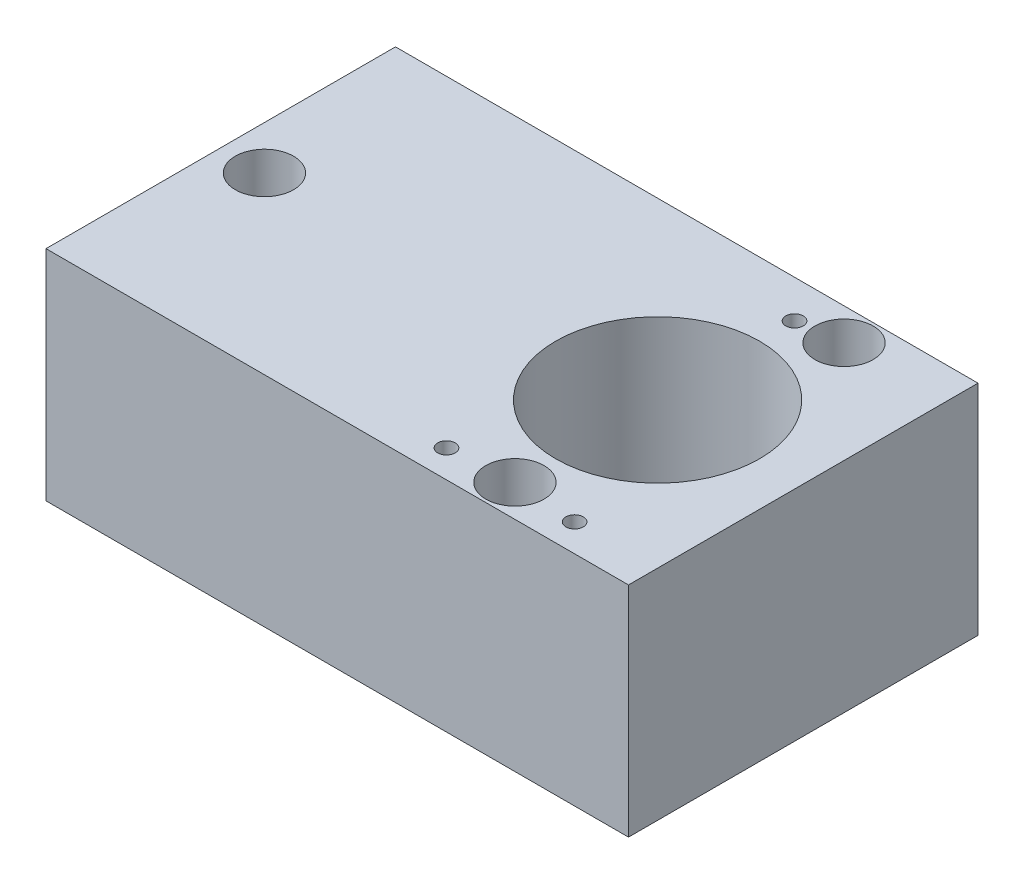
SolidWorks part; units mm, degrees
ref_plane "前视基准面" through (0, 0, 0) normal (0, 0, 1) x (1, 0, 0)
ref_plane "上视基准面" through (0, 0, 0) normal (0, 1, 0) x (1, 0, 0)
ref_plane "右视基准面" through (0, 0, 0) normal (1, 0, 0) x (0, 0, -1)
other "Configuration Table"
sketch "草图1" plane through (0, 0, 0) normal (0, 1, 0) x (1, 0, 0)
  line L0 (7.8359, -6) -> (30.681, -6) construction
  line L1 (0, 0) -> (20, 0)
  line L2 (0, 0) -> (0, -12)
  line L3 (0, -12) -> (20, -12)
  line L4 (20, 0) -> (20, -12)
  circle A7 centre (5, -6) radius 1
  circle A8 centre (8.3407, -8.2) radius 0.55
  circle A9 centre (10.7299, -3.8078) radius 0.55
  circle A10 centre (15, -6) radius 2.55
  circle A11 centre (15, -6) radius 3.5
  point P5 (5, -6)
  point P16 (0, 0)
  point P17 (0, 0)
  point P19 (0, 0)
  point P20 (0, 0)
  dimension "D4" = 1.1
  dimension "D6" = 7
  dimension "D8" = 2
  dimension "D3" = 1.1
  dimension "D5" = 5.1
  dimension "D2" = 5
  dimension "D7" = 20
  dimension "D10" = 5
  dimension "D12" = 12
extrude "凸台-拉伸1" add sketch "草图1" along normal blind 2.5 contours L4 L3 L2 L1
extrude "切除-拉伸3" cut sketch "草图1<9>" along normal blind 2.5 contours A9 | A10 | A8
sketch "草图1<9>" plane through (0, 0, 0) normal (0, 1, 0) x (1, 0, 0) same geometry as "草图1"
extrude "凸台-拉伸2" add sketch "草图1<10>" along normal blind 5 from surface contours L1 L4 L3 L2 | A11 starting at face at (8.3407, 2.5, 8.75)
sketch "草图1<10>" plane through (0, 0, 0) normal (0, 1, 0) x (1, 0, 0) same geometry as "草图1"
sketch "草图2" plane through (0, 0, 0) normal (0, -1, 0) x (1, 0, 0)
  circle A0 centre (15, 10.9) radius 0.7
  circle A1 centre (1.5, 6) radius 0.7
  circle A2 centre (16.5, 1.1) radius 0.7
  circle A3 centre (16.5, 1.1) radius 1
  circle A4 centre (15, 10.9) radius 1
  circle A5 centre (1.5, 6) radius 1
  circle A9 centre (12.8, 11.05) radius 0.3
  circle A16 centre (17.2, 11.05) radius 0.3
  circle A17 centre (15, 1.3) radius 0.3
  circle A18 centre (1.5, 6) radius 0.3
  dimension "D1" = 1.4
  dimension "D2" = 2
  dimension "D3" = 0.6
extrude "切除-拉伸4" cut sketch "草图2" against normal through all contours A0 | A2 | A1
extrude "切除-拉伸5" cut sketch "草图2<3>" along normal offset from surface (5.5 mm away) 2 from surface contours A4 | A5 | A3 up to face at (15, 0, 10.2) starting at face at (15, 7.5, 10.2)
sketch "草图2<3>" plane through (0, 0, 0) normal (0, -1, 0) x (1, 0, 0) same geometry as "草图2"
extrude "切除-拉伸6" cut sketch "草图2<6>" along normal blind 6 from surface contours A9 | A16 | A17 starting at face at (15, 7.5, 11.9)
sketch "草图2<6>" plane through (0, 0, 0) normal (0, -1, 0) x (1, 0, 0) same geometry as "草图2"
